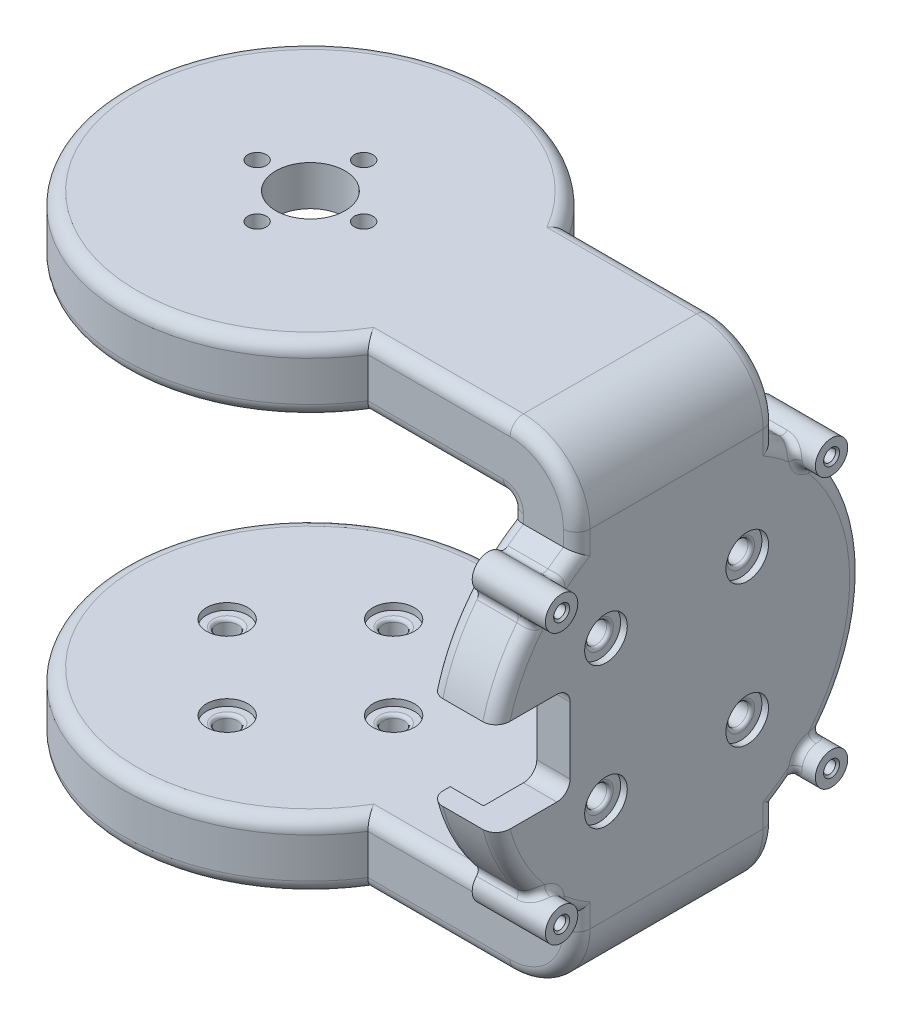
SolidWorks part; units mm, degrees
ref_plane "前视基准面" through (0, 0, 0) normal (0, 0, 1) x (1, 0, 0)
ref_plane "上视基准面" through (0, 0, 0) normal (0, 1, 0) x (1, 0, 0)
ref_plane "右视基准面" through (0, 0, 0) normal (1, 0, 0) x (0, 0, -1)
other "Configuration Table"
sketch "草图1" plane through (0, 0, 0) normal (0, 0, 1) x (1, 0, 0)
  line L0 (0, 0) -> (28, 0)
  line L1 (28, 0) -> (28, -10)
  line L2 (28, -10) -> (25, -10)
  line L3 (25, -10) -> (25, -5)
  line L4 (25, -5) -> (0, -5)
  line L5 (0, -5) -> (0, 0)
revolve "旋转1" add sketch "草图1" angle 360 about L5
sketch "草图2" plane through (0, 0, 0) normal (0, 1, 0) x (1, 0, 0)
  circle A0 centre (12.5, 0) radius 1.6
  circle A1 centre (0, -12.5) radius 1.6
  circle A2 centre (-12.5, 0) radius 1.6
  circle A3 centre (0, 12.5) radius 1.6
  point P13 (0, 0)
  dimension "D1" = 4
extrude "切除-拉伸1" cut sketch "草图2" against normal blind 10
sketch "草图3" plane through (0, 0, 0) normal (0, 1, 0) x (1, 0, 0)
  circle A0 centre (0, 12.5) radius 3.1
  circle A1 centre (12.5, 0) radius 3.1
  circle A2 centre (0, -12.5) radius 3.1
  circle A3 centre (-12.5, 0) radius 3.1
  point P12 (0, 0)
  dimension "D1" = 4
extrude "切除-拉伸2" cut sketch "草图3" against normal blind 1
fillet "圆角3" radius 0.5 4 edges at (0, -1, -10.9) (-12.5, -1, 1.6) (0, -1, 14.1) (12.5, -1, 1.6)
sketch "草图4" plane through (0, 0, 0) normal (0, 1, 0) x (1, 0, 0)
  line L0 (0, 0) -> (28, 0)
  circle A0 centre (0, 0) radius 28 construction
ref_plane "基准面1" through (0, 0, 0) normal (0, 0, 1) x (1, 0, 0)
sketch "草图6" plane through (0, 0, 0) normal (0, 1, 0) x (1, 0, 0)
  line L0 (55, 15) -> (55, -15)
  line L3 (55, 15) -> (23.6432, 15)
  line L5 (55, -15) -> (23.6432, -15)
  arc A0 (23.6432, -15) -> (23.6432, 15) centre (0, 0) ccw
extrude "凸台-拉伸1" add sketch "草图6" against normal blind 10
sketch "草图7" plane through (0, 0, 0) normal (0, 0, 1) x (1, 0, 0)
  line L1 (45, 52) -> (0, 52)
  line L3 (55, 62) -> (0, 62)
  line L4 (0, 62) -> (0, 52)
  line L6 (45, 52) -> (45, 0)
  line L7 (23.6432, 0) -> (55, 0) construction
  line L8 (45, 0) -> (55, 0)
  line L9 (55, 62) -> (55, 0)
extrude "凸台-拉伸2" add sketch "草图7" along normal mid plane 30
sketch "草图8" plane through (55, 0, 0) normal (1, 0, 0) x (0, 0, -1)
  circle A0 centre (0, 26) radius 25
extrude "凸台-拉伸3" add sketch "草图8" against normal blind 10
sketch "草图9" plane through (45, 0, 0) normal (-1, 0, 0) x (0, 0, 1)
  circle A0 centre (0, 26) radius 25
extrude "切除-拉伸3" cut sketch "草图9" against normal blind 5
sketch "草图10" plane through (55, 0, 0) normal (1, 0, 0) x (0, 0, -1)
  line L0 (-15, 2.3568) -> (-15, 6)
  line L1 (-15, -10) -> (-15, 6) construction
  line L2 (-15, 46) -> (-15, 62) construction
  line L3 (15, 49.6432) -> (15, 46)
  line L4 (15, 46) -> (15, 62) construction
  line L5 (15, -10) -> (15, 6) construction
  line L6 (-15, 46) -> (-15, 49.6432)
  line L7 (15, 6) -> (15, 2.3568)
  arc A0 (-15, 46) -> (-15, 6) centre (0, 26) ccw
  arc A1 (-15, 49.6432) -> (-15, 2.3568) centre (0, 26) ccw
  arc A2 (15, 6) -> (15, 46) centre (0, 26) ccw
  arc A3 (15, 2.3568) -> (15, 49.6432) centre (0, 26) ccw
extrude "凸台-拉伸4" add sketch "草图10" against normal blind 10
sketch "草图11" plane through (55, 0, 0) normal (1, 0, 0) x (0, 0, -1)
  circle A0 centre (10.6066, 36.6066) radius 1.6
  circle A1 centre (10.6066, 15.3934) radius 1.6
  circle A2 centre (-10.6066, 15.3934) radius 1.6
  circle A3 centre (-10.6066, 36.6066) radius 1.6
  point P13 (0, 26)
  dimension "D1" = 4
extrude "切除-拉伸4" cut sketch "草图11" against normal blind 10
sketch "草图12" plane through (55, 0, 0) normal (1, 0, 0) x (0, 0, -1)
  circle A0 centre (-10.6066, 36.6066) radius 3.2
  circle A1 centre (10.6066, 36.6066) radius 3.2
  circle A4 centre (10.6066, 15.3934) radius 3.2
  circle A5 centre (-10.6066, 15.3934) radius 3.2
extrude "切除-拉伸5" cut sketch "草图12" against normal blind 1
fillet "圆角4" radius 0.5 4 edges at (54, 15.3934, 9.0066) (54, 36.6066, -12.2066) (54, 36.6066, 9.0066) (54, 15.3934, -12.2066)
fillet "圆角5" radius 1 2 edges at (45, 52, 0) (45, 0, 0)
fillet "圆角6" radius 10 2 edges at (55, 62, 0) (55, -10, 0)
sketch "草图13" plane through (0, 0, 0) normal (0, 0, 1) x (1, 0, 0)
  line L0 (-18.5, 52) -> (-28, 52)
  line L1 (-28, 52) -> (-28, 62)
  line L2 (-28, 62) -> (0, 62)
  line L3 (0, 56) -> (0, 62)
  line L4 (0, 62) -> (0, 52) construction
  line L5 (-11.5, 54) -> (-18.5, 54)
  line L6 (-18.5, 54) -> (-18.5, 52)
  line L7 (0, 56) -> (-11.5, 56)
  line L8 (-11.5, 56) -> (-11.5, 54)
revolve "旋转2" add sketch "草图13" angle 360 about L3
sketch "草图14" plane through (0, 52, 0) normal (0, -1, 0) x (1, 0, 0)
  line L0 (0, 15) -> (0, -15) construction
  circle A0 centre (0, 0) radius 18.5
extrude "切除-拉伸6" cut sketch "草图14" against normal blind 2
sketch "草图15" plane through (0, 54, 0) normal (0, -1, 0) x (1, 0, 0)
  line L0 (0, 11.5) -> (0, -11.5) construction
  circle A0 centre (0, 0) radius 11.5
extrude "切除-拉伸7" cut sketch "草图15" against normal blind 2
sketch "草图16" plane through (0, 56, 0) normal (0, -1, 0) x (1, 0, 0)
  line L0 (0, 0) -> (8, 0)
  circle A0 centre (8, 0) radius 1.4
  circle A1 centre (0, -8) radius 1.4
  circle A2 centre (-8, 0) radius 1.4
  circle A3 centre (0, 8) radius 1.4
  circle A4 centre (0, 0) radius 5.2
  point P13 (0, 0)
  dimension "D1" = 4
extrude "切除-拉伸8" cut sketch "草图16" against normal blind 13 contours A4 | A2 | A3 | A0 | A1 region at (-5.0529, 56, 0)
fillet "圆角7" radius 1 1 edges at (11.5, 54, 0)
fillet "圆角8" radius 2 32 edges at (33.8216, 52, 15) (45, 50.3216, 15) (55, 50.8216, 15) (34.3216, 62, 15) (34.3216, -10, 15) (55, 1.1784, 15) (45, 1.6784, 15) (33.8216, 0, 15) (55, 1.1784, -15) (34.3216, -10, -15) (33.8216, 0, -15) (45, 1.6784, -15) (34.3216, 62, -15) (55, 50.8216, -15) (45, 50.3216, -15) (33.8216, 52, -15) (-28, -10, 0) (-28, 62, 0) (-28, 52, 0) (-28, 0, 0) (45, 26, 28) (44.7071, 51.7071, 15) (52.0711, 59.0711, 15) (52.0711, -7.0711, 15) (55, 26, -28) (45, 26, -28) (55, 26, 28) (44.7071, 0.2929, 15) (52.0711, -7.0711, -15) (44.7071, 0.2929, -15) (52.0711, 59.0711, -15) (44.7071, 51.7071, -15)
sketch "草图17" plane through (55, 0, 0) normal (1, 0, 0) x (0, 0, -1)
  line L1 (-28, 26) -> (-28, 33)
  line L2 (-28, 33) -> (-16, 33)
  line L3 (-16, 33) -> (-16, 19)
  line L4 (-16, 19) -> (-28, 19)
  line L5 (-28, 19) -> (-28, 26)
  arc A0 (-15, 49.6432) -> (-15, 2.3568) centre (0, 26) ccw construction
extrude "切除-拉伸9" cut sketch "草图17" against normal blind 16
fillet "圆角9" radius 2 2 edges at (52.5, 19, 16) (52.5, 33, 16)
sketch "草图18" plane through (55, 0, 0) normal (1, 0, 0) x (0, 0, -1)
  circle A0 centre (20.27, 46.27) radius 0.9
  circle A1 centre (20.27, 46.27) radius 2.43
  circle A2 centre (20.27, 5.73) radius 2.43
  circle A3 centre (20.27, 5.73) radius 0.9
  circle A4 centre (-20.27, 5.73) radius 2.43
  circle A5 centre (-20.27, 5.73) radius 0.9
  circle A6 centre (-20.27, 46.27) radius 2.43
  circle A7 centre (-20.27, 46.27) radius 0.9
  point P19 (0, 26)
  dimension "D1" = 4
extrude "凸台-拉伸5" add sketch "草图18" against normal blind 8
sketch "草图19" plane through (55, 0, 0) normal (1, 0, 0) x (0, 0, -1)
  circle A0 centre (-20.27, 46.27) radius 0.9
  circle A1 centre (20.27, 46.27) radius 0.9
  circle A2 centre (20.27, 5.73) radius 0.9
  circle A3 centre (-20.27, 5.73) radius 0.9
extrude "切除-拉伸10" cut sketch "草图19" against normal blind 15
sketch "草图20" plane through (55, 0, 0) normal (1, 0, 0) x (0, 0, -1)
  circle A0 centre (20.27, 5.73) radius 2.43
  circle A1 centre (20.27, 5.73) radius 0.9
  circle A2 centre (-20.27, 5.73) radius 0.9
  circle A3 centre (-20.27, 5.73) radius 2.43
  circle A4 centre (-20.27, 46.27) radius 0.9
  circle A5 centre (-20.27, 46.27) radius 2.43
  circle A6 centre (20.27, 46.27) radius 0.9
  circle A7 centre (20.27, 46.27) radius 2.43
extrude "凸台-拉伸6" add sketch "草图20" along normal blind 3
fillet "圆角10" radius 1 12 edges at (54.9778, 7.0425, 18.2249) (50, 7.9001, 21.3634) (50, 4.6366, 18.0999) (54.9778, 7.7751, -18.9575) (54.9778, 44.9575, -18.2249) (54.9778, 44.2249, 18.9575) (50, 4.6366, -18.0999) (50, 7.9001, -21.3634) (50, 44.0999, -21.3634) (50, 47.3634, -18.0999) (50, 47.3634, 18.0999) (50, 44.0999, 21.3634)
chamfer "倒角1" distance 0.3 angle 45 4 edges at (58, 46.27, -21.17) (58, 46.27, 19.37) (58, 5.73, 19.37) (58, 5.73, -21.17)
chamfer "倒角2" distance 0.3 angle 45 4 edges at (9.4, 56, 0) (1.4, 56, 8) (-6.6, 56, 0) (1.4, 56, -8)
